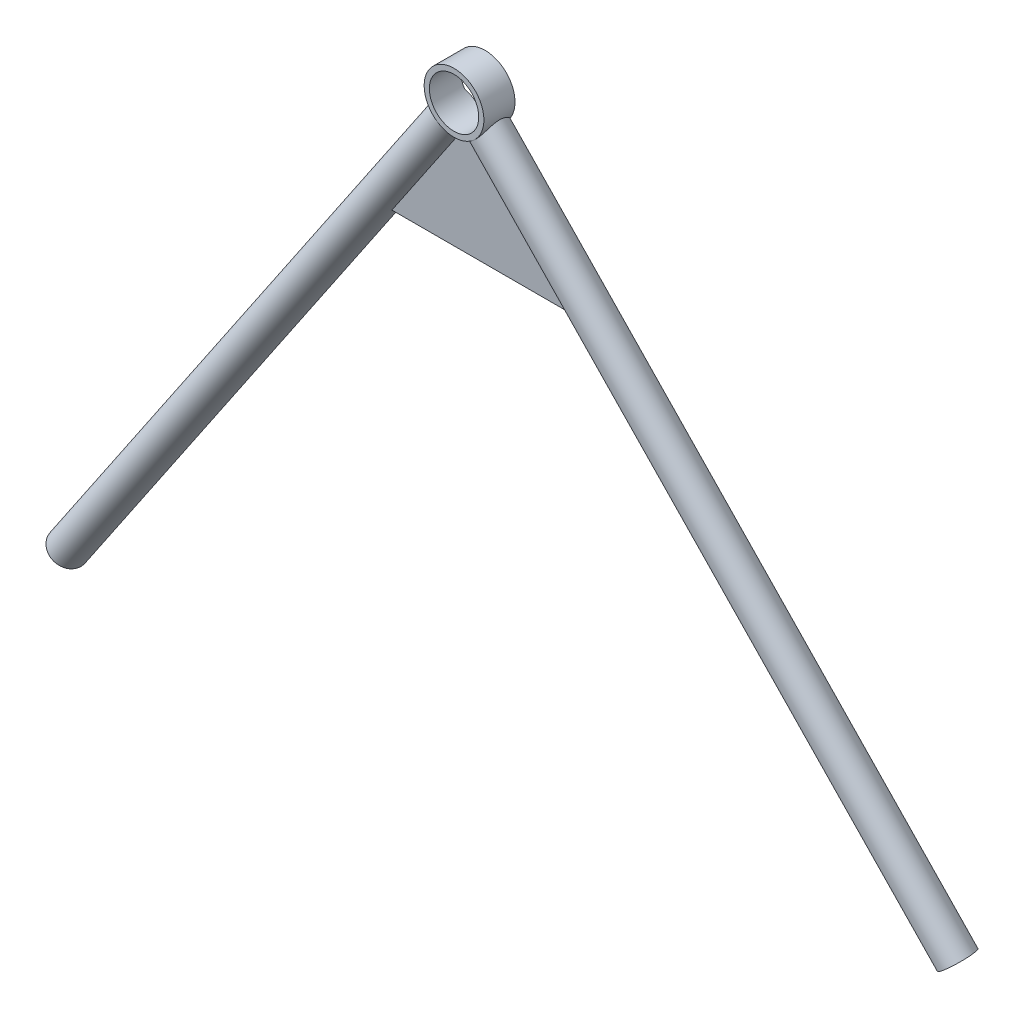
SolidWorks part; units mm, degrees
ref_plane "Front Plane" through (0, 0, 0) normal (0, 0, 1) x (1, 0, 0)
ref_plane "Top Plane" through (0, 0, 0) normal (0, 1, 0) x (1, 0, 0)
ref_plane "Right Plane" through (0, 0, 0) normal (1, 0, 0) x (0, 0, -1)
ref_plane "Plane1" through (0, 0, 205) normal (0, 0, 1) x (1, 0, 0)
sketch "Sketch1" plane through (0, 0, 205) normal (0, 0, 1) x (1, 0, 0)
  circle A0 centre (738.34, 550.67) radius 9.525
  circle A1 centre (738.34, 550.67) radius 11.525
  point P0 (738.34, 550.67)
  dimension "D1" = 19.05
  dimension "D2" = 2
extrude "Boss-Extrude1" add sketch "Sketch1" along normal mid plane 12
sketch3d "3DSketch1"
  line L0 (738.34, 550.67, 205) -> (538.06, 265.48, 182.39) construction
  line L1 (738.34, 550.67, 205) -> (538.06, 265.48, 182.39) construction
  line L2 (738.34, 550.67, 205) -> (563.5808, 301.8206, 185.2711)
  dimension "D1" = 44.5
sketch3d "3DSketch2"
  line L0 (937.75, 304.08, 185.45) -> (738.34, 550.67, 205) construction
  line L1 (937.75, 304.08, 185.45) -> (738.34, 550.67, 205) construction
  line L2 (738.34, 550.67, 205) -> (909.8215, 338.6163, 188.1881)
  dimension "D1" = 44.5
sweep "Sweep-Thin1" add path "3DSketch1" circular profile diameter 12.7 parameters "D1"=1, "D3"=12.7
sweep "Sweep-Thin2" add path "3DSketch2" circular profile diameter 12.7 parameters "D1"=1, "D3"=12.7
sketch3d "3DSketch3"
  line L0 (937.75, 304.08, 185.45) -> (738.34, 550.67, 205) construction
  line L1 (738.34, 550.67, 205) -> (538.06, 265.48, 182.39) construction
  line L2 (937.75, 304.08, 185.45) -> (738.34, 550.67, 205)
  line L3 (738.34, 550.67, 205) -> (538.06, 265.48, 182.39)
  point P0 (738.34, 550.67, 205)
  point P2 (709.53, 528.41, 34.08)
  point P4 (709.53, 275.7, 445.87)
ref_plane "Vertical" through (546.4447, -123.8137, -75.9828) normal (0.9664, -0.219, -0.1344) x (-0.1344, 0.015, -0.9908)
ref_plane "WishbonePLane" through (0.0001, -12.7115, 160.3351) normal (0, -0.079, 0.9969) x (1, 0, 0)
sketch "Sketch2" plane through (0.0001, -12.7115, 160.3351) normal (0, -0.079, 0.9969) x (1, 0, 0)
  line L0 (738.3399, 565.1493) -> (538.0599, 279.0644) construction
  line L1 (937.7499, 317.7855) -> (738.3399, 565.1493) construction
  line L2 (738.3399, 565.1493) -> (538.0599, 279.0644)
  line L3 (937.7499, 317.7855) -> (738.3399, 565.1493)
  line L4 (783.2409, 509.4506) -> (699.3468, 509.4506)
  point P3 (709.53, 529.4506)
  dimension "D1" = 20
extrude "Boss-Extrude2" add sketch "Sketch2" along normal mid plane 5 contours L4 L3 L2 region at (740.3093, 513.6537, 202.0653)
extrude "Cut-Extrude1" cut sketch "Sketch1<4>" against normal through all both and the other way through all contours A0 region at (738.34, 550.67, 205)
sketch "Sketch1<4>" plane through (0, 0, 205) normal (0, 0, 1) x (1, 0, 0) same geometry as "Sketch1"
ref_plane "Plane4" through (170.9248, -137.5099, -10.902) normal (0.7782, -0.6261, -0.0496) x (-0.0496, 0.0175, -0.9986)
